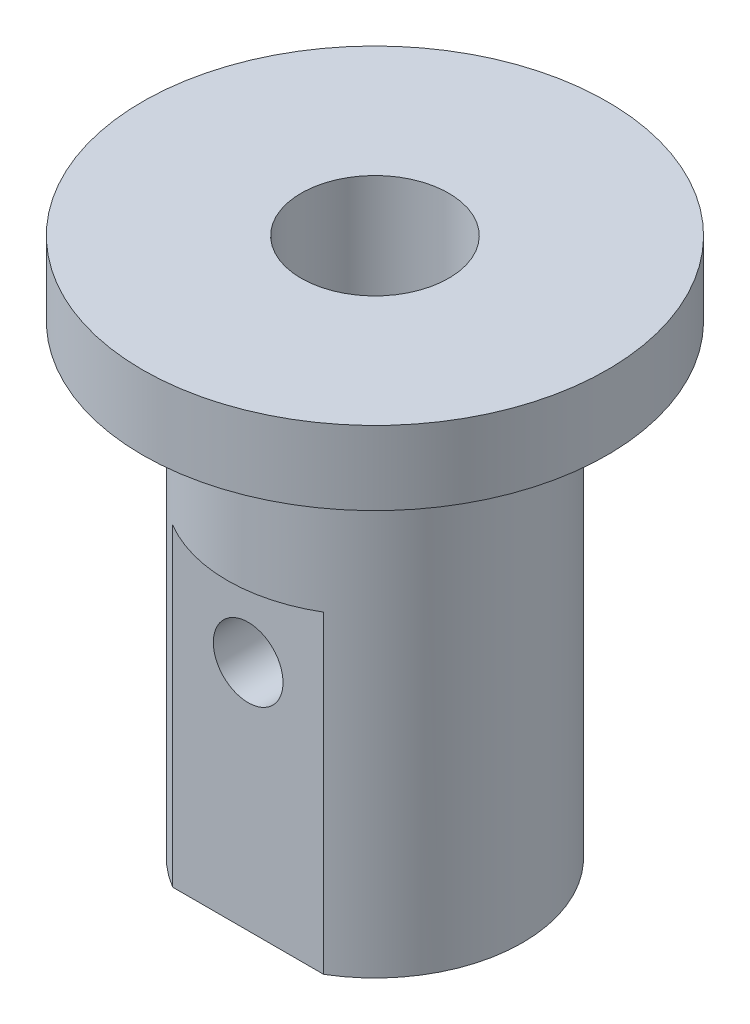
SolidWorks part; units mm, degrees
material "ABS"
ref_plane "Front Plane" through (0, 0, 0) normal (0, 0, 1) x (1, 0, 0)
ref_plane "Top Plane" through (0, 0, 0) normal (0, 1, 0) x (1, 0, 0)
ref_plane "Right Plane" through (0, 0, 0) normal (1, 0, 0) x (0, 0, -1)
sketch "Sketch1" plane through (0, 0, 0) normal (0, 1, 0) x (1, 0, 0)
  circle A0 centre (0, 0) radius 6.35
  circle A1 centre (0, 0) radius 3.175
  dimension "D1" = 6.35
  dimension "D2" = 12.7
extrude "Boss-Extrude1" add sketch "Sketch1" along normal blind 20
sketch "Sketch2" plane through (0, 20, 0) normal (0, 1, 0) x (1, 0, 0)
  circle A0 centre (0, 0) radius 3.175
  circle A1 centre (0, 0) radius 10
  circle A2 centre (0, 0) radius 3.175 construction
  dimension "D1" = 20
extrude "Boss-Extrude2" add sketch "Sketch2" along normal blind 3.175
sketch "Sketch3" plane through (0, 0, 0) normal (0, 0, 1) x (1, 0, 0)
  circle A0 centre (0, 10) radius 1.5
  dimension "D1" = 3
  dimension "D2" = 10
extrude "Cut-Extrude1" cut sketch "Sketch3" against normal through all and the other way blind 10
sketch "Sketch4" plane through (0, 0, 0) normal (0, -1, 0) x (1, 0, 0)
  line L1 (3.25, -5.4553) -> (-3.25, -5.4553)
  line L2 (3.25, -5.4553) -> (3.25, -6.35)
  line L3 (3.25, -6.35) -> (-3.25, -6.35)
  line L4 (-3.25, -5.4553) -> (-3.25, -6.35)
  line L5 (3.25, -5.4553) -> (-3.25, -6.35) construction
  line L6 (3.25, -6.35) -> (-3.25, -5.4553) construction
  line L7 (3.25, 5.4553) -> (-3.25, 5.4553)
  line L8 (3.25, 5.4553) -> (3.25, 6.35)
  line L9 (3.25, 6.35) -> (-3.25, 6.35)
  line L10 (-3.25, 5.4553) -> (-3.25, 6.35)
  line L11 (3.25, 5.4553) -> (-3.25, 6.35) construction
  line L12 (3.25, 6.35) -> (-3.25, 5.4553) construction
  circle A0 centre (0, 0) radius 6.35 construction
  point P4 (0, -5.9026)
  point P11 (0, 5.9026)
  point P12 (0, 0)
  point P13 (0, 0)
  point P14 (0, 0)
  point P15 (0, 0)
  point P16 (0, -6.0194)
  dimension "D1" = 6.5
extrude "Cut-Extrude2" cut sketch "Sketch4" against normal blind 13.5
